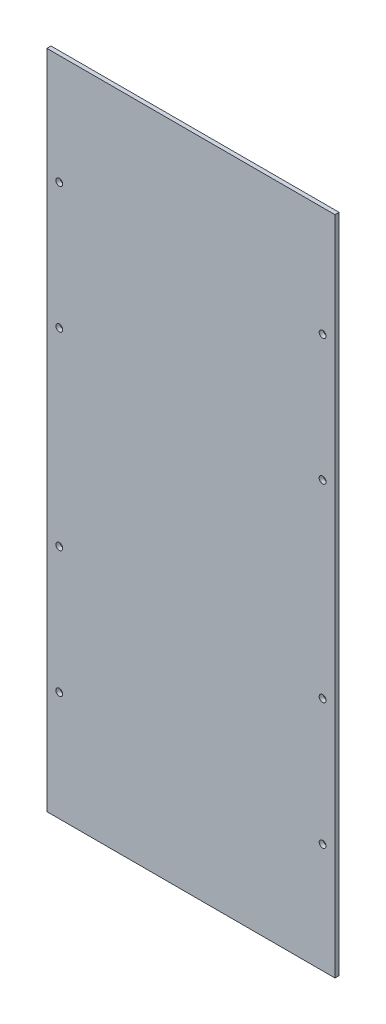
SolidWorks part; units mm, degrees
ref_plane "Alzado" through (0, 0, 0) normal (0, 0, 1) x (1, 0, 0)
ref_plane "Planta" through (0, 0, 0) normal (0, 1, 0) x (1, 0, 0)
ref_plane "Vista lateral" through (0, 0, 0) normal (1, 0, 0) x (0, 0, -1)
sketch "Croquis1" plane through (0, 0, 0) normal (0, 0, 1) x (1, 0, 0)
  line L1 (-90.5016, 703.6284) -> (119.4984, 703.6284)
  line L2 (-90.5016, 703.6284) -> (-90.5016, 1185.6284)
  line L3 (-90.5016, 1185.6284) -> (119.4984, 1185.6284)
  line L4 (119.4984, 703.6284) -> (119.4984, 1185.6284)
  circle A0 centre (110.4984, 1105.6384) radius 2.5
  circle A1 centre (-81.5016, 1105.6384) radius 2.5
  circle A2 centre (-81.5016, 1013.6384) radius 2.5
  circle A3 centre (110.4984, 1013.6384) radius 2.5
  circle A4 centre (-81.5016, 875.6184) radius 2.5
  circle A5 centre (110.4984, 783.6184) radius 2.5
  circle A6 centre (-81.5016, 783.6184) radius 2.5
  circle A7 centre (110.4984, 875.6184) radius 2.5
  dimension "D1" = 210
extrude "Saliente-Extruir1" add sketch "Croquis1" along normal blind 3
